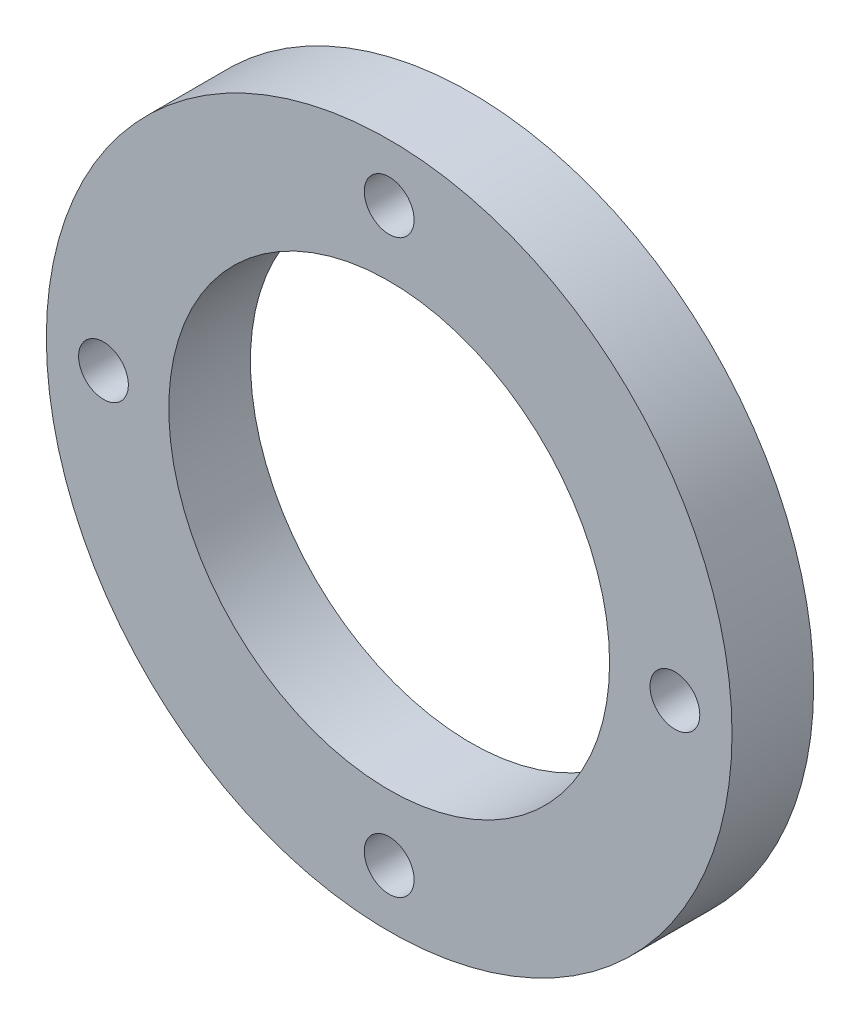
SolidWorks part; units mm, degrees
material "6061 Alloy"
ref_plane "Front Plane" through (0, 0, 0) normal (0, 0, 1) x (1, 0, 0)
ref_plane "Top Plane" through (0, 0, 0) normal (0, 1, 0) x (1, 0, 0)
ref_plane "Right Plane" through (0, 0, 0) normal (1, 0, 0) x (0, 0, -1)
sketch "Sketch1" plane through (0, 0, 0) normal (0, 0, 1) x (1, 0, 0)
  circle A1 centre (31.5, 5) radius 1.5 construction
  circle A2 centre (49, 22.5) radius 1.5 construction
  circle A3 centre (66.5, 5) radius 1.5 construction
  circle A4 centre (49, -12.5) radius 1.5 construction
  circle A5 centre (49, 5) radius 13
  circle A6 centre (31.5, 5) radius 1.5
  circle A7 centre (49, 22.5) radius 1.5
  circle A8 centre (66.5, 5) radius 1.5
  circle A9 centre (49, -12.5) radius 1.5
  arc A10 (49, -16) -> (49, 26) centre (49, 5) ccw construction
  circle A11 centre (49, 5) radius 21
extrude "Boss-Extrude1" add sketch "Sketch1" along normal blind 5
sketch "Sketch2" plane through (0, 0, 5) normal (0, 0, 1) x (1, 0, 0)
  circle A0 centre (49, 5) radius 13.5
  dimension "D1" = 27
extrude "Cut-Extrude1" cut sketch "Sketch2" against normal blind 10
sketch "Sketch3" plane through (0, 0, 5) normal (0, 0, 1) x (1, 0, 0)
  circle A0 centre (49, 22.5) radius 1.525
  circle A1 centre (31.5, 5) radius 1.525
  circle A2 centre (66.5, 5) radius 1.525
  circle A3 centre (49, -12.5) radius 1.525
  dimension "D1" = 3.05
extrude "Cut-Extrude2" cut sketch "Sketch3" against normal blind 10
